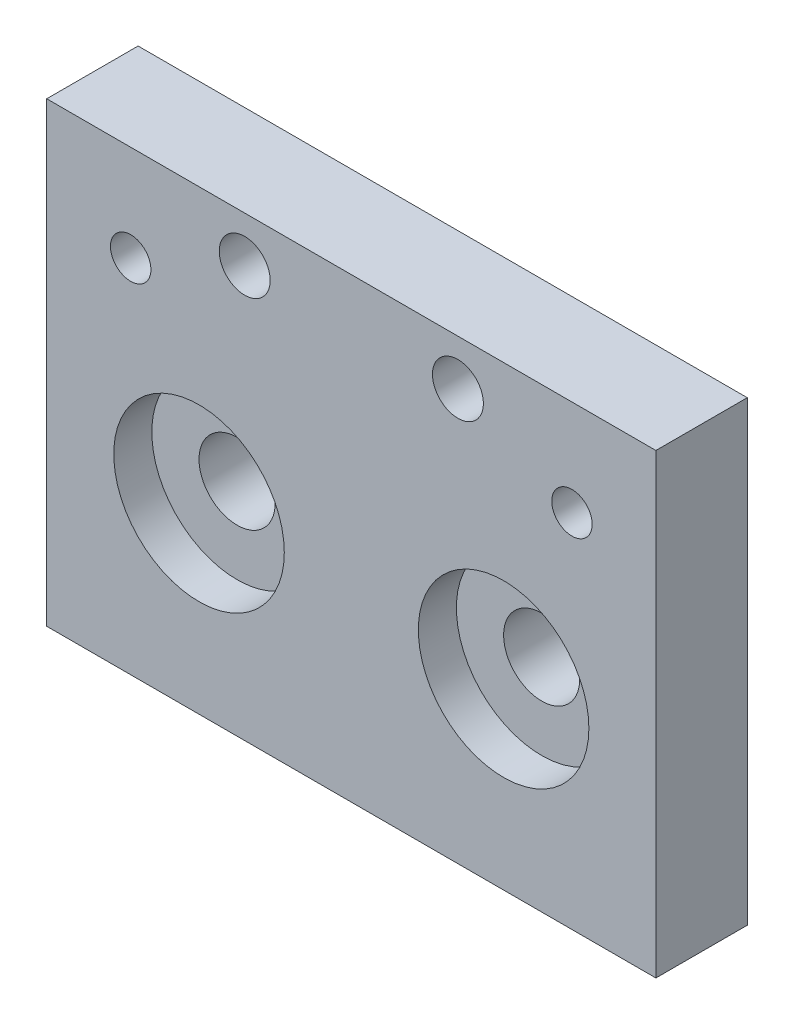
SolidWorks part; units mm, degrees
ref_plane "Front Plane" through (0, 0, 0) normal (0, 0, 1) x (1, 0, 0)
ref_plane "Top Plane" through (0, 0, 0) normal (0, 1, 0) x (1, 0, 0)
ref_plane "Right Plane" through (0, 0, 0) normal (1, 0, 0) x (0, 0, -1)
sketch "Sketch1" plane through (0, 0, 0) normal (0, 0, 1) x (1, 0, 0)
  line L0 (31.75, -9.525) -> (-31.75, -9.525) construction
  line L1 (-31.75, 0) -> (31.75, 0)
  line L2 (-31.75, 0) -> (-31.75, -47.625)
  line L3 (-31.75, -47.625) -> (31.75, -47.625)
  line L4 (31.75, 0) -> (31.75, -47.625)
  line L5 (31.75, -9.525) -> (31.75, 0) construction
  line L6 (0, -9.525) -> (0, -47.625) construction
  circle A0 centre (11.1125, -4.7625) radius 2.1 construction
  circle A1 centre (-11.1125, -4.7625) radius 2.1 construction
  circle A2 centre (11.1125, -4.7625) radius 2.1 construction
  circle A3 centre (-11.1125, -4.7625) radius 2.1 construction
  circle A4 centre (-11.1125, -4.7625) radius 2.6543
  circle A5 centre (11.1125, -4.7625) radius 2.6543
  circle A8 centre (-15.875, -28.575) radius 3.9687
  circle A9 centre (-15.875, -28.575) radius 8.89
  circle A10 centre (-171.45, -17.4815) radius 3.9687 construction
  circle A11 centre (-171.45, -17.4815) radius 8.89 construction
  circle A12 centre (15.875, -28.575) radius 3.9687
  circle A13 centre (15.875, -28.575) radius 8.89
  point P23 (0, -28.575)
  dimension "D2" = 5.3086
  dimension "D3" = 38.1
  dimension "D1" = 47.625
  dimension "D4" = 31.75
extrude "Boss-Extrude1" add sketch "Sketch1" along normal blind 9.525 contours L4 L1 L2 L3 A9 A5 A4 A13 | A9 A8 | A13 A12 region at (0, -23.1998, 0) region at (-24.5136, -28.575, 0) region at (7.2364, -28.575, 0)
extrude "Cut-Extrude2" cut sketch "Sketch1<3>" against normal offset from surface 5.5575 and the other way through all from surface contours A9 A8 | A13 A12 region at (-24.5136, -28.575, 0) region at (7.2364, -28.575, 0) up to face at (13.7668, -4.7625, 0) starting at face at (13.7668, -4.7625, 9.525)
sketch "Sketch1<3>" plane through (0, 0, 0) normal (0, 0, 1) x (1, 0, 0) same geometry as "Sketch1"
sketch "Sketch2" plane through (0, 0, 9.525) normal (0, 0, 1) x (1, 0, 0)
  line L2 (0, 0) -> (0, -47.625)
  line L3 (-31.75, 0) -> (31.75, 0) construction
  line L4 (-31.75, -47.625) -> (31.75, -47.625) construction
  circle A0 centre (22.9997, -10) radius 2.1082
  circle A2 centre (-22.9997, -10) radius 2.1082
  dimension "D1" = 4.2164
  dimension "D2" = 45.9994
  dimension "D3" = 10
extrude "Cut-Extrude3" cut sketch "Sketch2" against normal through all contours A0 | A2 region at (22.9997, -10, 9.525) region at (-22.9997, -10, 9.525)
